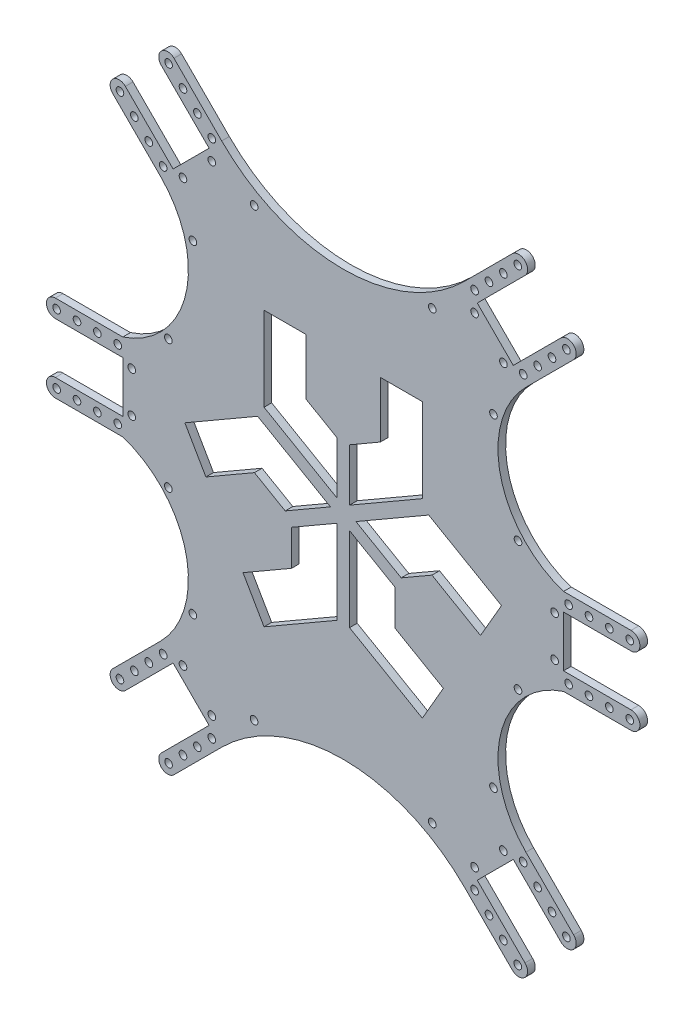
SolidWorks part; units mm, degrees
ref_plane "Płaszczyzna przednia" through (0, 0, 0) normal (0, 0, 1) x (1, 0, 0)
ref_plane "Płaszczyzna górna" through (0, 0, 0) normal (0, 1, 0) x (1, 0, 0)
ref_plane "Płaszczyzna prawa" through (0, 0, 0) normal (1, 0, 0) x (0, 0, -1)
sketch "Model" plane through (0, 0, 0) normal (0, 0, 1) x (1, 0, 0)
  line L0 (2252.0948, 928.366) -> (2233.3565, 947.1043)
  line L1 (2209.3149, 923.0627) -> (2228.0532, 904.3244)
  line L2 (2247.1451, 923.4163) -> (2228.4067, 942.1546)
  line L3 (2233.0029, 909.2741) -> (2247.1451, 923.4163)
  line L4 (2214.2646, 928.0125) -> (2233.0029, 909.2741)
  line L5 (2385.3188, 928.0125) -> (2366.5805, 909.2741)
  line L6 (2213.2789, 842.2855) -> (2186.7789, 842.2855)
  line L7 (2186.7789, 808.2855) -> (2213.2789, 808.2855)
  line L8 (2213.2789, 835.2855) -> (2186.7789, 835.2855)
  line L9 (2213.2789, 815.2855) -> (2213.2789, 835.2855)
  line L10 (2186.7789, 815.2855) -> (2213.2789, 815.2855)
  line L11 (2412.8046, 815.2855) -> (2386.3046, 815.2855)
  line L12 (2386.3046, 815.2855) -> (2386.3046, 835.2855)
  line L13 (2386.3046, 835.2855) -> (2412.8046, 835.2855)
  line L14 (2412.8046, 808.2855) -> (2386.3046, 808.2855)
  line L15 (2347.4886, 722.2049) -> (2366.2269, 703.4666)
  line L16 (2390.2686, 727.5082) -> (2371.5302, 746.2466)
  line L17 (2352.4384, 727.1547) -> (2371.1767, 708.4163)
  line L18 (2366.5805, 741.2968) -> (2352.4384, 727.1547)
  line L19 (2385.3188, 722.5585) -> (2366.5805, 741.2968)
  line L20 (2214.2646, 722.5585) -> (2233.0029, 741.2968)
  line L21 (2233.0029, 741.2968) -> (2247.1451, 727.1547)
  line L22 (2247.1451, 727.1547) -> (2228.4067, 708.4163)
  line L23 (2209.3149, 727.5082) -> (2228.0532, 746.2466)
  line L24 (2386.3046, 842.2855) -> (2412.8046, 842.2855)
  line L25 (2149.0438, 825.2855) -> (2431.0142, 825.2855) construction
  line L31 (2366.5805, 909.2741) -> (2352.4384, 923.4163)
  line L32 (2352.4384, 923.4163) -> (2371.1767, 942.1546)
  line L33 (2390.2686, 923.0627) -> (2371.5302, 904.3244)
  line L34 (2347.4886, 928.366) -> (2366.2269, 947.1043)
  line L35 (2252.0948, 722.2049) -> (2233.3565, 703.4666)
  line L66 (2299.7917, 657.0048) -> (2299.7917, 965.92) construction
  line L68 (2268.7129, 879.1156) -> (2268.7129, 846.1156)
  line L69 (2361.9494, 825.2855) -> (2333.3706, 841.7855)
  line L70 (2302.2917, 787.9553) -> (2302.2917, 820.9553)
  line L71 (2268.7129, 846.1156) -> (2297.2917, 829.6156)
  line L72 (2353.6994, 810.996) -> (2334.6406, 821.9997)
  line L73 (2330.8706, 846.1156) -> (2302.2917, 829.6156)
  line L74 (2333.3706, 841.7855) -> (2304.7917, 825.2855)
  line L75 (2330.8706, 771.4553) -> (2339.1206, 785.7448)
  line L76 (2279.5217, 810.6958) -> (2297.2917, 820.9553)
  line L77 (2277.0217, 815.0259) -> (2264.9429, 821.9997)
  line L78 (2322.5617, 815.0259) -> (2334.6406, 821.9997)
  line L79 (2266.2129, 841.7855) -> (2294.7917, 825.2855)
  line L80 (2339.1206, 785.7448) -> (2320.0617, 796.7484)
  line L81 (2302.2917, 850.1347) -> (2314.3706, 857.1084)
  line L82 (2237.634, 825.2855) -> (2266.2129, 841.7855)
  line L83 (2268.7129, 771.4553) -> (2260.4629, 785.7448)
  line L84 (2285.2129, 879.1156) -> (2285.2129, 857.1084)
  line L85 (2330.8706, 771.4553) -> (2302.2917, 787.9553)
  line L86 (2302.2917, 850.1347) -> (2302.2917, 829.6156)
  line L87 (2320.0617, 810.6958) -> (2320.0617, 796.7484)
  line L88 (2297.2917, 787.9553) -> (2297.2917, 820.9553)
  line L89 (2330.8706, 879.1156) -> (2314.3706, 879.1156)
  line L90 (2237.634, 825.2855) -> (2245.884, 810.996)
  line L91 (2297.2917, 850.1347) -> (2285.2129, 857.1084)
  line L92 (2277.0217, 815.0259) -> (2294.7917, 825.2855)
  line L93 (2260.4629, 785.7448) -> (2279.5217, 796.7484)
  line L94 (2268.7129, 879.1156) -> (2285.2129, 879.1156)
  line L95 (2279.5217, 810.6958) -> (2279.5217, 796.7484)
  line L96 (2330.8706, 879.1156) -> (2330.8706, 846.1156)
  line L97 (2314.3706, 879.1156) -> (2314.3706, 857.1084)
  line L98 (2245.884, 810.996) -> (2264.9429, 821.9997)
  line L99 (2320.0617, 810.6958) -> (2302.2917, 820.9553)
  line L100 (2297.2917, 850.1347) -> (2297.2917, 829.6156)
  line L101 (2322.5617, 815.0259) -> (2304.7917, 825.2855)
  line L102 (2361.9494, 825.2855) -> (2353.6994, 810.996)
  line L103 (2268.7129, 771.4553) -> (2297.2917, 787.9553)
  arc A0 (2252.0948, 722.2049) -> (2347.4886, 722.2049) centre (2299.7917, 674.508) cw
  arc A1 (2186.7789, 808.2855) -> (2186.7789, 815.2855) centre (2186.7789, 811.7855) cw
  arc A2 (2186.7789, 835.2855) -> (2186.7789, 842.2855) centre (2186.7789, 838.7855) cw
  arc A3 (2347.4886, 928.366) -> (2252.0948, 928.366) centre (2299.7917, 976.0629) cw
  arc A4 (2371.5302, 746.2466) -> (2386.3046, 808.2855) centre (2398.0042, 772.7206) cw
  circle A5 centre (2248.2057, 927.3054) radius 1.5
  circle A6 centre (2248.2057, 919.5272) radius 1.5
  arc A7 (2228.0532, 904.3244) -> (2213.2789, 842.2855) centre (2201.5792, 877.8504) cw
  circle A8 centre (2229.1139, 908.2135) radius 1.5
  circle A9 centre (2223.457, 913.8703) radius 1.5
  circle A10 centre (2217.8001, 919.5272) radius 1.5
  circle A11 centre (2212.1433, 925.184) radius 1.5
  arc A12 (2209.3149, 923.0627) -> (2214.2646, 928.0125) centre (2211.7897, 925.5376) cw
  circle A13 centre (2236.892, 908.2135) radius 1.5
  circle A14 centre (2231.2352, 944.2759) radius 1.5
  circle A15 centre (2236.892, 938.6191) radius 1.5
  circle A16 centre (2242.5489, 932.9622) radius 1.5
  arc A17 (2228.4067, 942.1546) -> (2233.3565, 947.1043) centre (2230.8816, 944.6295) cw
  circle A18 centre (2351.3777, 723.2656) radius 1.5
  circle A19 centre (2382.8046, 833.2855) radius 1.5
  circle A20 centre (2187.2789, 838.7855) radius 1.5
  circle A21 centre (2195.2789, 838.7855) radius 1.5
  circle A22 centre (2203.2789, 838.7855) radius 1.5
  circle A23 centre (2187.2789, 811.7855) radius 1.5
  circle A24 centre (2195.2789, 811.7855) radius 1.5
  circle A25 centre (2203.2789, 811.7855) radius 1.5
  circle A26 centre (2211.2789, 811.7855) radius 1.5
  circle A27 centre (2216.7789, 817.2855) radius 1.5
  circle A28 centre (2211.2789, 838.7855) radius 1.5
  circle A29 centre (2216.7789, 833.2855) radius 1.5
  circle A30 centre (2388.3046, 838.7855) radius 1.5
  circle A31 centre (2351.3777, 731.0438) radius 1.5
  circle A32 centre (2382.8046, 817.2855) radius 1.5
  circle A33 centre (2370.4696, 742.3575) radius 1.5
  circle A34 centre (2376.1264, 736.7006) radius 1.5
  circle A35 centre (2381.7833, 731.0438) radius 1.5
  circle A36 centre (2387.4401, 725.3869) radius 1.5
  arc A37 (2390.2686, 727.5082) -> (2385.3188, 722.5585) centre (2387.7937, 725.0333) cw
  circle A38 centre (2362.6914, 742.3575) radius 1.5
  circle A39 centre (2368.3483, 706.295) radius 1.5
  circle A43 centre (2362.6914, 711.9519) radius 1.5
  circle A44 centre (2357.0346, 717.6087) radius 1.5
  arc A45 (2371.1767, 708.4163) -> (2366.2269, 703.4666) centre (2368.7018, 705.9415) cw
  circle A46 centre (2388.3046, 811.7855) radius 1.5
  circle A47 centre (2396.3046, 811.7855) radius 1.5
  circle A48 centre (2404.3046, 811.7855) radius 1.5
  arc A49 (2228.4067, 708.4163) -> (2233.3565, 703.4666) centre (2230.8816, 705.9415) ccw
  circle A50 centre (2242.5489, 717.6087) radius 1.5
  circle A51 centre (2412.3046, 811.7855) radius 1.5
  circle A52 centre (2396.3046, 838.7855) radius 1.5
  circle A53 centre (2404.3046, 838.7855) radius 1.5
  circle A54 centre (2412.3046, 838.7855) radius 1.5
  arc A55 (2371.5302, 904.3244) -> (2386.3046, 842.2855) centre (2398.0042, 877.8504) ccw
  arc A56 (2412.8046, 835.2855) -> (2412.8046, 842.2855) centre (2412.8046, 838.7855) ccw
  arc A57 (2412.8046, 808.2855) -> (2412.8046, 815.2855) centre (2412.8046, 811.7855) ccw
  circle A63 centre (2236.892, 711.9519) radius 1.5
  arc A64 (2371.1767, 942.1546) -> (2366.2269, 947.1043) centre (2368.7018, 944.6295) ccw
  circle A65 centre (2357.0346, 932.9622) radius 1.5
  circle A66 centre (2362.6914, 938.6191) radius 1.5
  circle A67 centre (2368.3483, 944.2759) radius 1.5
  circle A68 centre (2362.6914, 908.2135) radius 1.5
  arc A69 (2390.2686, 923.0627) -> (2385.3188, 928.0125) centre (2387.7937, 925.5376) ccw
  circle A70 centre (2387.4401, 925.184) radius 1.5
  circle A71 centre (2381.7833, 919.5272) radius 1.5
  circle A72 centre (2376.1264, 913.8703) radius 1.5
  circle A73 centre (2370.4696, 908.2135) radius 1.5
  circle A75 centre (2351.3777, 919.5272) radius 1.5
  circle A76 centre (2351.3777, 927.3054) radius 1.5
  circle A78 centre (2231.2352, 706.295) radius 1.5
  circle A79 centre (2236.892, 742.3575) radius 1.5
  arc A83 (2209.3149, 727.5082) -> (2214.2646, 722.5585) centre (2211.7897, 725.0333) ccw
  circle A84 centre (2212.1433, 725.3869) radius 1.5
  circle A85 centre (2217.8001, 731.0438) radius 1.5
  circle A86 centre (2223.457, 736.7006) radius 1.5
  circle A87 centre (2229.1139, 742.3575) radius 1.5
  arc A88 (2228.0532, 746.2466) -> (2213.2789, 808.2855) centre (2201.5792, 772.7206) ccw
  circle A89 centre (2248.2057, 731.0438) radius 1.5
  circle A90 centre (2248.2057, 723.2656) radius 1.5
  point P3 (2252.0948, 928.366)
  point P8 (2299.7917, 825.2855)
extrude "Dodanie-wyciągnięcie1" add sketch "Model" along normal blind 3
sketch "Szkic1" plane through (0, 0, 3) normal (0, 0, -1) x (-1, 0, 0)
  circle A0 centre (-2334.7607, 912.8097) radius 1.5
  circle A1 centre (-2358.8023, 888.768) radius 1.5
  circle A2 centre (-2368.4429, 850.5595) radius 1.5
  circle A3 centre (-2368.4429, 800.0114) radius 1.5
  circle A4 centre (-2358.8023, 761.8029) radius 1.5
  circle A5 centre (-2334.7607, 737.7613) radius 1.5
  circle A6 centre (-2264.8227, 737.7613) radius 1.5
  circle A7 centre (-2240.7811, 761.8029) radius 1.5
  circle A8 centre (-2231.1406, 800.0114) radius 1.5
  circle A9 centre (-2231.1406, 850.5595) radius 1.5
  circle A10 centre (-2240.7811, 888.768) radius 1.5
  circle A11 centre (-2264.8227, 912.8097) radius 1.5
extrude "Wytnij-wyciągnięcie2" cut sketch "Szkic1" along normal through all
